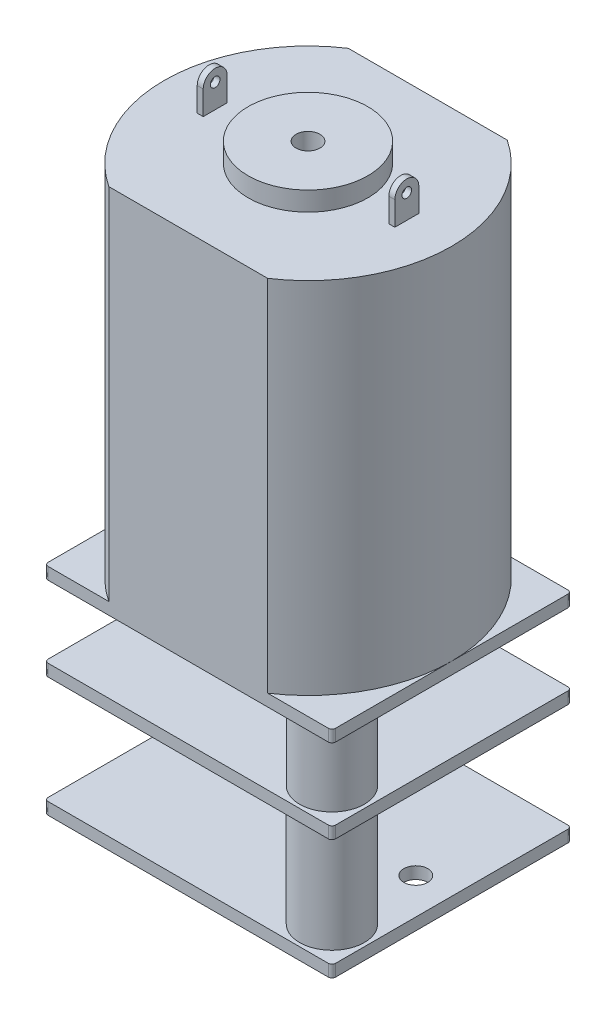
SolidWorks part; units mm, degrees
ref_plane "Front Plane" through (0, 0, 0) normal (0, 0, 1) x (1, 0, 0)
ref_plane "Top Plane" through (0, 0, 0) normal (0, 1, 0) x (1, 0, 0)
ref_plane "Right Plane" through (0, 0, 0) normal (1, 0, 0) x (0, 0, -1)
sketch "Sketch1" plane through (0, 0, 0) normal (0, 1, 0) x (1, 0, 0)
  line L0 (0, 6.9616) -> (0, -9.0069) construction
  line L1 (-3.3166, -5) -> (3.3166, -5)
  line L3 (-3.3166, 5) -> (3.3166, 5)
  line L5 (-4.7551, -3.6591) -> (4.7551, 3.6591) construction
  line L6 (-4.7551, 3.6591) -> (4.7551, -3.6591) construction
  line L7 (-9.6714, 0) -> (12.5877, 0) construction
  line L8 (4.125, 0.5) -> (3.875, -0.5) construction
  line L9 (-4.125, -0.5) -> (-3.875, -0.5)
  line L10 (-4.125, -0.5) -> (-4.125, 0.5)
  line L11 (-4.125, 0.5) -> (-3.875, 0.5)
  line L12 (-3.875, -0.5) -> (-3.875, 0.5)
  line L13 (-4.125, -0.5) -> (-3.875, 0.5) construction
  line L14 (-4.125, 0.5) -> (-3.875, -0.5) construction
  line L19 (4.125, -0.5) -> (3.875, 0.5) construction
  line L20 (4.125, 0.5) -> (3.875, 0.5)
  line L21 (4.125, -0.5) -> (4.125, 0.5)
  line L22 (4.125, -0.5) -> (3.875, -0.5)
  line L23 (3.875, -0.5) -> (3.875, 0.5)
  arc A0 (-3.3166, 5) -> (-3.3166, -5) centre (0, 0) ccw
  arc A1 (3.3166, -5) -> (3.3166, 5) centre (0, 0) ccw
  circle A2 centre (0, 0) radius 2.5
  circle A3 centre (0, 0) radius 0.5
  point P0 (0, 0)
  point P15 (-4, 0)
  point P24 (4, 0)
  dimension "D2" = 8
  dimension "D3" = 5
  dimension "D4" = 6
  dimension "D5" = 1
  dimension "D1" = 10
  dimension "D6" = 1
  dimension "D7" = 0.25
extrude "Boss-Extrude1" add sketch "Sketch1" against normal blind 15 contours L1 A1 L3 A0 A2 L22 L23 L20 L21 L12 L9 L10 L11 | A2 A3 | L9 L12 L11 L10 | A3 | L23 L22 L21 L20 region at (-5.8438, 0, 0) region at (-4, 0, 0) region at (4, 0, 0) region at (-2.4293, 0, 0) region at (0, 0, 0)
extrude "Boss-Extrude2" add sketch "Sketch1<3>" along normal blind 0.8 contours A2 A3 region at (-2.4293, 0, 0)
sketch "Sketch1<3>" plane through (0, 0, 0) normal (0, 1, 0) x (1, 0, 0) same geometry as "Sketch1"
extrude "Boss-Extrude3" add sketch "Sketch1<5>" along normal blind 1.5 contours L12 L11 L10 L9
sketch "Sketch1<5>" plane through (0, 0, 0) normal (0, 1, 0) x (1, 0, 0) same geometry as "Sketch1"
sketch "Sketch2" plane through (-4.125, 0, 0) normal (-1, 0, 0) x (0, 0, 1)
  line L0 (-0.5, 1) -> (-0.5, 0)
  line L1 (5, 0) -> (-5, 0) construction
  line L2 (0.5, 1.5) -> (-0.5, 1.5) construction
  line L3 (-0.5, 0) -> (0.5, 0)
  line L4 (0.5, 0) -> (-0.5, 0) construction
  line L5 (0.5, 0) -> (0.5, 1)
  line L6 (-0.5, 1.5) -> (-0.5, 0) construction
  line L7 (-0.5, 1) -> (-0.5, 1.5)
  line L8 (-0.5, 1.5) -> (0.5, 1.5)
  line L9 (0.5, 1.5) -> (0.5, 1)
  arc A0 (0.5, 1) -> (-0.5, 1) centre (0, 1) ccw
  circle A1 centre (0, 1) radius 0.2005
  line M2 (0.5, 0) -> (0.5, 1.5)
  line M3 (0.5, 1.5) -> (-0.5, 1.5)
  line M4 (-0.5, 1.5) -> (-0.5, 0)
  dimension "D1" = 1
  dimension "D2" = 0.4011
extrude "Cut-Extrude3" cut sketch "Sketch2" against normal blind 1.5 contours A1 | A0 L8 M4 | A0 M2 M3 region at (-4.125, 1.3883, -0.3883) region at (-4.125, 1.3883, 0.3883) region at (-4.125, 1, 0)
mirror "Mirror1" about plane through (0, 0, 0) normal (1, 0, 0) of "Boss-Extrude3", "Cut-Extrude3"
sketch "Sketch3" plane through (0, -15, 0) normal (0, -1, 0) x (1, 0, 0)
  line L1 (-5.8485, -5) -> (5.8485, -5)
  line L2 (-6, -4.8485) -> (-6, 4.8485)
  line L3 (-5.8485, 5) -> (5.8485, 5)
  line L4 (6, -4.8485) -> (6, 4.8485)
  line L5 (-6, -5) -> (6, 5) construction
  line L9 (-10.8151, 0) -> (10.0529, 0) construction
  line L13 (-6, 5) -> (6, -5) construction
  arc A0 (-5.8485, -5) -> (-6, -4.8485) centre (-5.8485, -4.8485) cw
  arc A1 (5.8485, -5) -> (6, -4.8485) centre (5.8485, -4.8485) ccw
  arc A2 (5.8485, 5) -> (6, 4.8485) centre (5.8485, 4.8485) cw
  arc A3 (-6, 4.8485) -> (-5.8485, 5) centre (-5.8485, 4.8485) cw
  point P0 (0, 0)
  point P18 (0, 0)
  point P19 (0, 0)
  dimension "D1" = 0.1515
  dimension "D2" = 10
  dimension "D3" = 12
extrude "Boss-Extrude4" add sketch "Sketch3" along normal blind 0.5
sketch "Sketch6" plane through (0, -15.5, 0) normal (0, -1, 0) x (1, 0, 0)
  line L0 (-6, -4.8485) -> (-6, 4.8485) construction
  line L1 (-5.8485, -5) -> (5.8485, -5) construction
  line L2 (-5.8485, 5) -> (5.8485, 5) construction
  line L3 (6, -4.8485) -> (6, 4.8485) construction
  circle A0 centre (-4.5, -3.5) radius 1.35
  circle A1 centre (4.5, 3.5) radius 1.35
  dimension "D1" = 2.7
  dimension "D2" = 2.7
  dimension "D3" = 1.5
  dimension "D4" = 1.5
  dimension "D5" = 1.5
  dimension "D6" = 1.5
sketch "Sketch7" plane through (0, -15.5, 0) normal (0, -1, 0) x (1, 0, 0)
  line L0 (-6, -4.8485) -> (-6, 4.8485)
  line L1 (-5.8485, 5) -> (5.8485, 5)
  line L2 (6, 4.8485) -> (6, -4.8485)
  line L3 (-5.8485, -5) -> (5.8485, -5)
  arc A0 (-6, -4.8485) -> (-5.8485, -5) centre (-5.8485, -4.8485) ccw
  arc A1 (6, -4.8485) -> (5.8485, -5) centre (5.8485, -4.8485) cw
  arc A2 (5.8485, 5) -> (6, 4.8485) centre (5.8485, 4.8485) cw
  arc A3 (-6, 4.8485) -> (-5.8485, 5) centre (-5.8485, 4.8485) cw
  point P10 (-6, -5)
  point P13 (6, -5)
  point P16 (6, 5)
  point P19 (-6, 5)
  dimension "D1" = 0.1515
extrude "Boss-Extrude6" add sketch "Sketch7" along normal blind 0.5 from offset 3
extrude "Boss-Extrude7" add sketch "Sketch6" along normal blind 8
sketch "Sketch9" plane through (0, -19, 0) normal (0, -1, 0) x (1, 0, 0)
  line L0 (-5.8485, 5) -> (5.8485, 5)
  line L1 (6, 4.8485) -> (6, -4.8485)
  line L2 (5.8485, -5) -> (-5.8485, -5)
  line L3 (-6, -4.8485) -> (-6, 4.8485)
  line L4 (-10.8151, 0) -> (10.0529, 0) construction
  line L5 (0, 6.0563) -> (0, -6.4497) construction
  line L6 (-6, 5) -> (6, -5) construction
  arc A0 (-5.8485, -5) -> (-6, -4.8485) centre (-5.8485, -4.8485) cw
  arc A1 (6, -4.8485) -> (5.8485, -5) centre (5.8485, -4.8485) cw
  arc A2 (5.8485, 5) -> (6, 4.8485) centre (5.8485, 4.8485) cw
  arc A3 (-5.8485, 5) -> (-6, 4.8485) centre (-5.8485, 4.8485) ccw
  circle A4 centre (-4.5, 0) radius 0.5
  circle A5 centre (4.5, 0) radius 0.5
  circle A6 centre (0, 0) radius 1.5
  point P10 (-6, -5)
  point P13 (6, -5)
  point P16 (6, 5)
  point P19 (-6, 5)
  dimension "D1" = 0.1515
  dimension "D2" = 1
  dimension "D4" = 3
  dimension "D3" = 9
extrude "Boss-Extrude9" add sketch "Sketch9" along normal blind 0.5 from offset 4.5
sketch "Sketch10" plane through (0, -24, 0) normal (0, -1, 0) x (1, 0, 0)
  circle A0 centre (0, 0) radius 2
  circle A1 centre (0, 0) radius 1.5
  dimension "D1" = 4
  dimension "D2" = 3
extrude "Boss-Extrude10" add sketch "Sketch10" along normal blind 0.5
fillet "Fillet1" radius 0.5 1 edges at (0, -24.5, -2)
sketch "Sketch11" plane through (0, -24, 0) normal (0, -1, 0) x (1, 0, 0)
  circle A0 centre (0, 0) radius 1.5
  dimension "D1" = 3
extrude "Boss-Extrude11" add sketch "Sketch11" against normal blind 0.5
